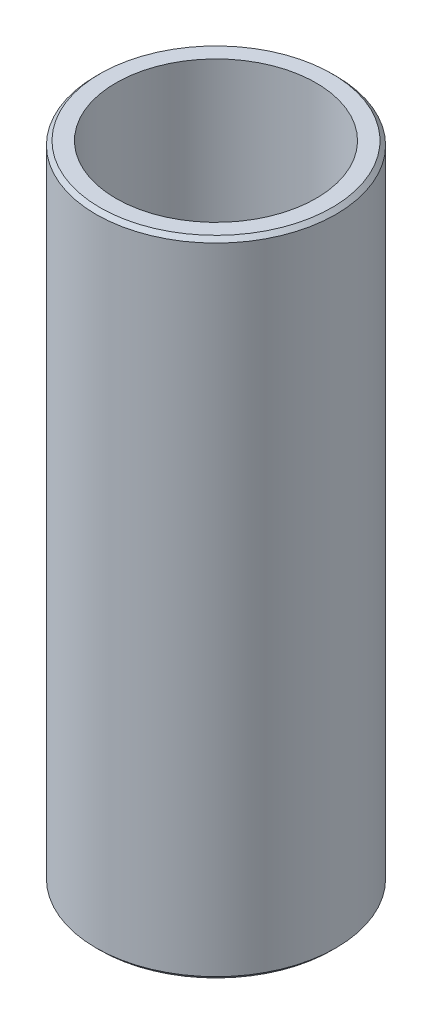
SolidWorks part; units mm, degrees
ref_plane "Front Plane" through (0, 0, 0) normal (0, 0, 1) x (1, 0, 0)
ref_plane "Top Plane" through (0, 0, 0) normal (0, 1, 0) x (1, 0, 0)
ref_plane "Right Plane" through (0, 0, 0) normal (1, 0, 0) x (0, 0, -1)
sketch "Sketch1" plane through (0, 0, 0) normal (0, 1, 0) x (1, 0, 0)
  circle A0 centre (0, 0) radius 50
  dimension "SHAFT_OD" = 100
extrude "Boss-Extrude1" add sketch "Sketch1" along normal blind 268.1447
sketch "Sketch2" plane through (0, 0, 0) normal (0, 1, 0) x (1, 0, 0)
  circle A0 centre (0, 0) radius 41.7348
  dimension "BORE_D" = 83.4696
extrude "Cut-Extrude1" cut sketch "Sketch2" along normal through all
chamfer "Chamfer1" distance 1.6395 angle 45 2 edges at (0, 268.1447, 50) (0, 0, 50)
